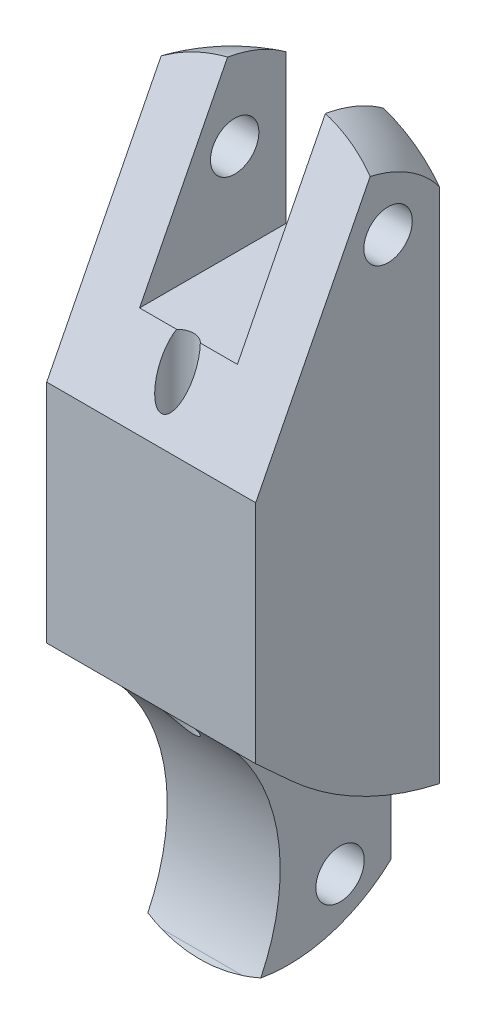
SolidWorks part; units mm, degrees
ref_plane "Front Plane" through (0, 0, 0) normal (0, 0, 1) x (1, 0, 0)
ref_plane "Top Plane" through (0, 0, 0) normal (0, 1, 0) x (1, 0, 0)
ref_plane "Right Plane" through (0, 0, 0) normal (1, 0, 0) x (0, 0, -1)
sketch "Sketch1" plane through (0, 0, 0) normal (0, 1, 0) x (1, 0, 0)
  circle A0 centre (0, 0) radius 10
extrude "Extrude1" add sketch "Sketch1" along normal blind 45
fillet "Fillet1" radius 10 1 edges at (0, 0, 10)
fillet "Скругление1" radius 8 1 edges at (0, 45, 10)
sketch "Sketch2" plane through (0, 0, 0) normal (0, 0, 1) x (1, 0, 0)
  line L0 (0, 40) -> (0, 29.5527) construction
  line L1 (3.5, 8.6646) -> (3.5, -4.7575)
  line L2 (-11.1723, 8.6646) -> (-3.5, 8.6646)
  line L3 (-11.1723, 8.6646) -> (-11.1723, -4.7575)
  line L4 (-11.1723, -4.7575) -> (-3.5, -4.7575)
  line L5 (-3.5, 8.6646) -> (-3.5, -4.7575)
  line L6 (11.1723, -4.7575) -> (3.5, -4.7575)
  line L7 (11.1723, 8.6646) -> (11.1723, -4.7575)
  line L8 (11.1723, 8.6646) -> (3.5, 8.6646)
  line L16 (10, 22.5) -> (24.8802, 22.5) construction
  dimension "D1" = 3.5
extrude "Extrude2" cut sketch "Sketch2" against normal mid plane 40
sketch "Sketch5" plane through (0, 0, 0) normal (0, 1, 0) x (1, 0, 0)
  line L0 (0, -10) -> (0, -4.7764) construction
  line L1 (12.9644, 10.9303) -> (6.4758, 10.9303)
  line L2 (-12.9644, -10.0291) -> (-6.4758, -10.0291)
  line L3 (-12.9644, -10.0291) -> (-12.9644, 10.9303)
  line L4 (-12.9644, 10.9303) -> (-6.4758, 10.9303)
  line L5 (-6.4758, -10.0291) -> (-6.4758, 10.9303)
  line L6 (6.4758, -10.0291) -> (6.4758, 10.9303)
  line L7 (12.9644, -10.0291) -> (6.4758, -10.0291)
  line L8 (12.9644, -10.0291) -> (12.9644, 10.9303)
extrude "Extrude4" cut sketch "Sketch5" along normal through all
sketch "Sketch7" plane through (0, 0, 0) normal (0, 1, 0) x (1, 0, 0)
  line L0 (0, 0) -> (11.986, 0) construction
  line L1 (-12.3124, -5) -> (12.0612, -5)
  line L2 (-12.3124, 12.9182) -> (12.0612, 12.9182)
  line L3 (-12.3124, 12.9182) -> (-12.3124, 6.375)
  line L4 (-12.3124, 6.375) -> (12.0612, 6.375)
  line L5 (12.0612, 12.9182) -> (12.0612, 6.375)
  line L6 (12.0612, -12.9182) -> (12.0612, -5)
  line L7 (-12.3124, -12.9182) -> (12.0612, -12.9182)
  line L8 (-12.3124, -12.9182) -> (-12.3124, -5)
  dimension "D1" = 5
extrude "Extrude6" cut sketch "Sketch7" against normal mid plane 92
sketch "Sketch10" plane through (3.5, 0, 0) normal (1, 0, 0) x (0, 0, -1)
  circle A0 centre (3.2028, 3.9183) radius 1.5
extrude "Cut-Extrude2" cut sketch "Sketch10" against normal through all
sketch "Sketch12" plane through (6.4758, 0, 0) normal (1, 0, 0) x (0, 0, -1)
  line L0 (-5, 15.4219) -> (2.3805, 8.6646)
  line L1 (-5, 8.6646) -> (-5, 42.0784) construction
  line L2 (-5, 8.6646) -> (6.375, 8.6646) construction
  line L3 (2.3805, 8.6646) -> (-3.3753, -2.4329)
  line L4 (-3.3753, -2.4329) -> (-5, -2.4329)
  line L5 (-5, -2.4329) -> (-5, 15.4219)
extrude "Cut-Extrude3" cut sketch "Sketch12" against normal through all
fillet "Fillet2" radius 12 1 edges at (0, 8.6646, -2.3805)
fillet "Fillet3" radius 20 2 edges at (-4.9879, 8.6646, -2.3805) (4.9879, 8.6646, -2.3805)
sketch "Эскиз1" plane through (0, 0, 5) normal (0, 0, 1) x (1, 0, 0)
  line L0 (0, 40) -> (0, 42.119) construction
  line L2 (2, 45) -> (-2, 45) construction
  line L3 (-3.0313, 56.0201) -> (3.0313, 56.0201)
  line L4 (-3.0313, 56.0201) -> (-3.0313, 33.9799)
  line L5 (-3.0313, 33.9799) -> (3.0313, 33.9799)
  line L6 (3.0313, 56.0201) -> (3.0313, 33.9799)
  line L7 (-3.0313, 56.0201) -> (3.0313, 33.9799) construction
  line L8 (-3.0313, 33.9799) -> (3.0313, 56.0201) construction
  point P1 (0, 45)
extrude "Вытянуть1" cut sketch "Эскиз1" against normal through all
sketch "Эскиз3" plane through (6.4758, 0, 0) normal (1, 0, 0) x (0, 0, -1)
  line L0 (3.2028, 3.9183) -> (3.2028, 12.7758) construction
  line L1 (3.2028, 45.5877) -> (-6.7849, 45.5877)
  line L2 (-6.7849, 45.5877) -> (-6.7849, 25.916)
  line L3 (-6.7849, 25.916) -> (3.2028, 45.5877)
  circle A0 centre (3.2028, 39.7136) radius 1.5
extrude "Вытянуть2" cut sketch "Эскиз3" against normal through all
sketch "Эскиз4" plane through (0, 33.9799, 0) normal (0, 1, 0) x (1, 0, 0)
  line L0 (0, -3.475) -> (0, -10.038) construction
  circle A0 centre (0, -3.3714) radius 1
extrude "Вытянуть3" cut sketch "Эскиз4" against normal through all
